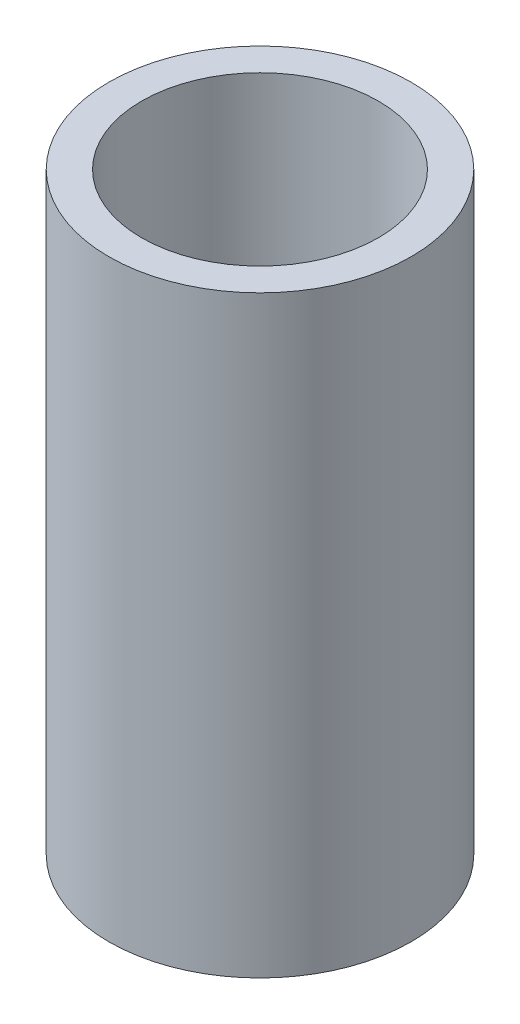
SolidWorks part; units mm, degrees
ref_plane "Front Plane" through (0, 0, 0) normal (0, 0, 1) x (1, 0, 0)
ref_plane "Top Plane" through (0, 0, 0) normal (0, 1, 0) x (1, 0, 0)
ref_plane "Right Plane" through (0, 0, 0) normal (1, 0, 0) x (0, 0, -1)
sketch "Sketch1" plane through (0, 0, 0) normal (0, 1, 0) x (1, 0, 0)
  circle A0 centre (0, 0) radius 17.5
  dimension "SLEEVE_OD" = 35
extrude "Boss-Extrude1" add sketch "Sketch1" along normal blind 68.6914
sketch "Sketch2" plane through (0, 0, 0) normal (0, 1, 0) x (1, 0, 0)
  circle A0 centre (0, 0) radius 13.7103
  dimension "BORE_D" = 27.4206
extrude "Cut-Extrude1" cut sketch "Sketch2" along normal through all
chamfer "Chamfer1" distance 2.2221 angle 36.252 rebuild error yes
